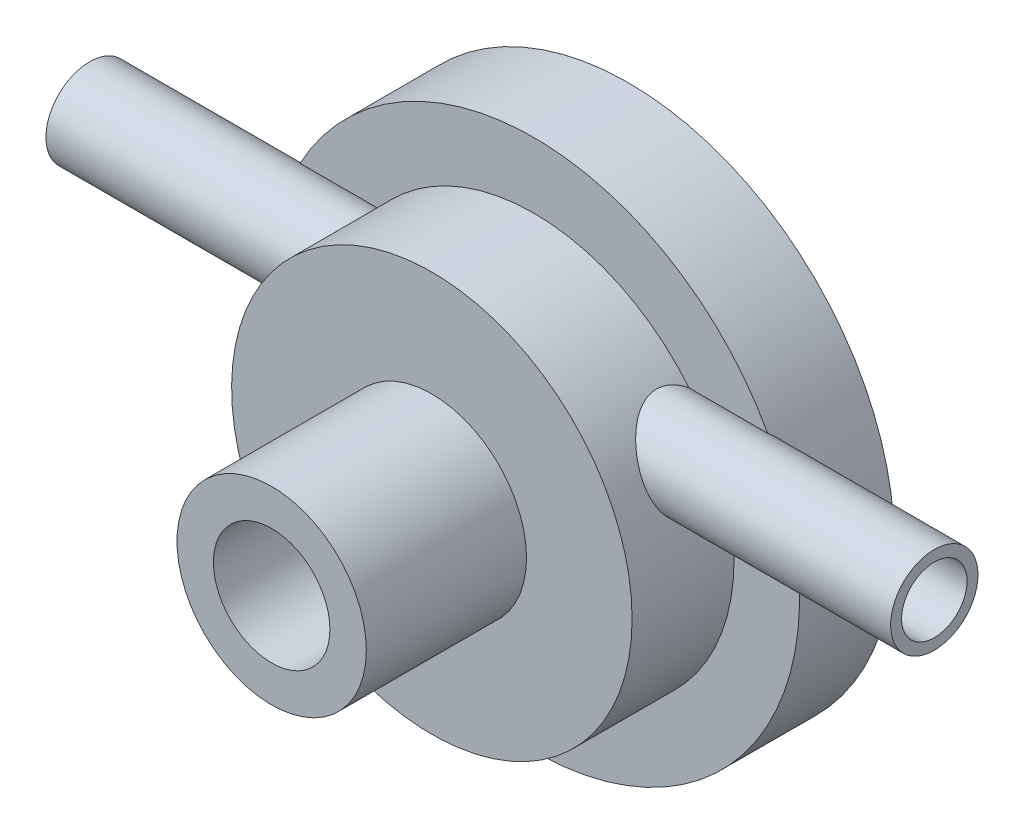
SolidWorks part; units mm, degrees
ref_plane "Front Plane" through (0, 0, 0) normal (0, 0, 1) x (1, 0, 0)
ref_plane "Top Plane" through (0, 0, 0) normal (0, 1, 0) x (1, 0, 0)
ref_plane "Right Plane" through (0, 0, 0) normal (1, 0, 0) x (0, 0, -1)
sketch "Sketch1" plane through (0, 0, 0) normal (0, 0, 1) x (1, 0, 0)
  circle A0 centre (0, 0) radius 36.5
  dimension "D1" = 73
extrude "Boss-Extrude1" add sketch "Sketch1" along normal blind 13
sketch "Sketch2" plane through (0, 0, 13) normal (0, 0, 1) x (1, 0, 0)
  circle A0 centre (0, 0) radius 27.5
  dimension "D1" = 55
extrude "Boss-Extrude2" add sketch "Sketch2" along normal blind 14
sketch "Sketch3" plane through (0, 0, 27) normal (0, 0, 1) x (1, 0, 0)
  circle A0 centre (0, 0) radius 13
  dimension "D1" = 26
extrude "Boss-Extrude3" add sketch "Sketch3" along normal blind 22
sketch "Sketch4" plane through (0, 0, 49) normal (0, 0, 1) x (1, 0, 0)
  circle A0 centre (0, 0) radius 8
  dimension "D1" = 16
extrude "Cut-Extrude1" cut sketch "Sketch4" against normal through all
ref_plane "Plane2" through (36.5, 0, 0) normal (1, 0, 0) x (0, 0, -1)
sketch "Sketch6" plane through (36.5, 0, 0) normal (1, 0, 0) x (0, 0, -1)
  line L0 (0, -36.5) -> (0, 36.5) construction
  line L2 (-13, 27.5) -> (-27, 27.5) construction
  circle A0 centre (-16.5, 12.5) radius 6
  dimension "D1" = 12
  dimension "D2" = 16.5
  dimension "D3" = 15
extrude "Boss-Extrude4" add sketch "Sketch6" along normal blind 22 and the other way blind 94
sketch "Sketch8" plane through (0, 0, 0) normal (0, 0, -1) x (-1, 0, 0)
  arc A0 (-18.1046, 13.3594) -> (18.1046, 13.3594) centre (0, 0) ccw
  circle A1 centre (0, 0) radius 8 construction
  arc A2 (18.1046, 13.3594) -> (-18.1046, 13.3594) centre (0, -8) ccw
  point P1 (0, 0)
  point P2 (0, -8)
  point P9 (0, 0)
extrude "Cut-Extrude2" cut sketch "Sketch8" against normal blind 13
sketch "Sketch10" plane through (58.5, 0, 0) normal (1, 0, 0) x (0, 0, -1)
  circle A0 centre (-16.5, 12.5) radius 4.5
  dimension "D1" = 9
extrude "Cut-Extrude3" cut sketch "Sketch10" against normal through all
